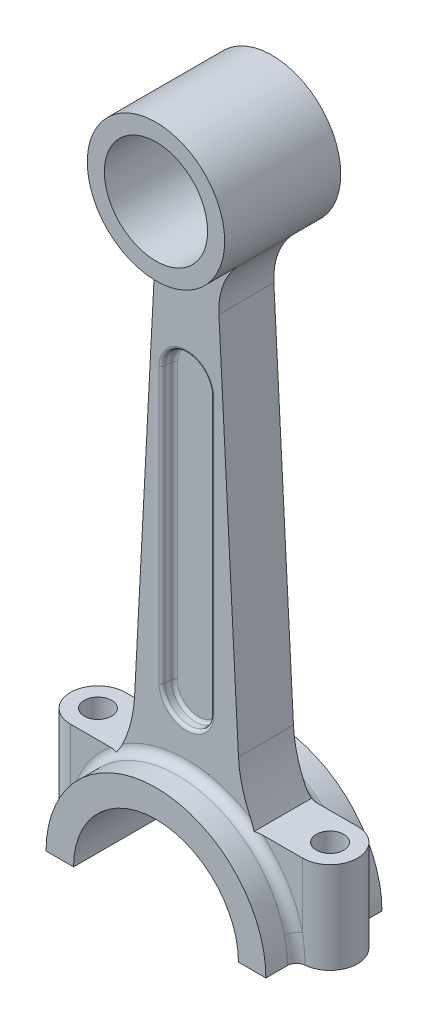
SolidWorks part; units mm, degrees
ref_plane "Front Plane" through (0, 0, 0) normal (0, 0, 1) x (1, 0, 0)
ref_plane "Top Plane" through (0, 0, 0) normal (0, 1, 0) x (1, 0, 0)
ref_plane "Right Plane" through (0, 0, 0) normal (1, 0, 0) x (0, 0, -1)
sketch "Sketch1" plane through (0, 0, 0) normal (0, 0, 1) x (1, 0, 0)
  line L0 (0, 0) -> (0, -202.2) construction
  line L1 (-10, -20.1556) -> (-17.9037, -170.9677)
  line L2 (10, -20.1556) -> (17.9037, -170.9677)
  line L3 (-36, -202.2) -> (-27, -202.2)
  line L4 (27, -202.2) -> (36, -202.2)
  circle A0 centre (0, 0) radius 22.5
  circle A1 centre (0, 0) radius 16.9
  arc A2 (27, -202.2) -> (-27, -202.2) centre (0, -202.2) ccw
  arc A3 (36, -202.2) -> (-36, -202.2) centre (0, -202.2) ccw
  dimension "D1" = 33.8
  dimension "D2" = 45
  dimension "D3" = 54
  dimension "D4" = 72
  dimension "D5" = 202.2
  dimension "D6" = 20
  dimension "D7" = 6
extrude "Boss-Extrude1" add sketch "Sketch1" along normal mid plane 38 contours A3 A2 | A0 | A1 | L3 A2 L4 A3 region at (0, -167.005, 0)
extrude "Boss-Extrude2" add sketch "Sketch1<3>" along normal mid plane 18 contours A0 L0 A3 L2 | L0 A0 L1 A3 region at (7.1998, -101.43, 0) region at (-7.1998, -101.43, 0)
sketch "Sketch1<3>" plane through (0, 0, 0) normal (0, 0, 1) x (1, 0, 0) same geometry as "Sketch1"
sketch "Sketch2" plane through (0, 0, 9) normal (0, 0, 1) x (1, 0, 0)
  line L0 (0, 0) -> (0, -202.2) construction
  line L1 (0, -56.1) -> (0, -146.1) construction
  line L2 (8, -56.1) -> (8, -146.1)
  line L3 (-8, -56.1) -> (-8, -146.1)
  arc A0 (8, -56.1) -> (-8, -56.1) centre (0, -56.1) ccw
  arc A1 (-8, -146.1) -> (8, -146.1) centre (0, -146.1) ccw
  point P6 (0, -101.1)
  dimension "D2" = 8
  dimension "D1" = 90
extrude "Cut-Extrude1" cut sketch "Sketch2" against normal blind 4
mirror "Mirror1" about plane through (0, 0, 0) normal (0, 0, 1) of "Cut-Extrude1"
fillet "Fillet1" radius 1 16 edges at (0, -48.1, -9) (8, -101.1, -9) (0, -154.1, -9) (0, -48.1, -5) (8, -101.1, -5) (0, -154.1, -5) (0, -48.1, 9) (8, -101.1, 9) (0, -154.1, 9) (0, -48.1, 5) (8, -101.1, 5) (0, -154.1, 5) (-8, -101.1, -9) (-8, -101.1, -5) (-8, -101.1, 9) (-8, -101.1, 5)
fillet "Fillet3" radius 40 2 edges at (-17.9037, -170.9677, 0) (17.9037, -170.9677, 0)
ref_plane "Plane1" through (0, -172.2, 0) normal (0, -1, 0) x (-1, 0, 0)
sketch "Sketch3" plane through (0, -172.2, 0) normal (0, -1, 0) x (-1, 0, 0)
  line L0 (-38, 0) -> (38, 0) construction
  line L1 (-38, 9) -> (38, 9)
  line L2 (-38, -9) -> (38, -9)
  arc A0 (-38, 9) -> (-38, -9) centre (-38, 0) ccw
  arc A1 (38, -9) -> (38, 9) centre (38, 0) ccw
  point P2 (0, 0)
  dimension "D2" = 9
  dimension "D1" = 76
extrude "Boss-Extrude3" add sketch "Sketch3" along normal up to surface (30 mm away) up to face at (31.5, -202.2, 0)
sketch "Sketch5" plane through (0, 0, -9) normal (0, 0, -1) x (-1, 0, 0)
  line L1 (-27, -202.2) -> (27, -202.2)
  line L2 (-27, -202.2) -> (27, -202.2)
  arc A1 (27, -202.2) -> (-27, -202.2) centre (0, -202.2) ccw
  arc A2 (27, -202.2) -> (-27, -202.2) centre (0, -202.2) ccw
  dimension "D1" = 0
extrude "Cut-Extrude2" cut sketch "Sketch5" against normal through all
sketch "Sketch6" plane through (0, -172.2, 0) normal (0, 1, 0) x (1, 0, 0)
  circle A0 centre (-38, 0) radius 4.5
  dimension "D1" = 9
extrude "Cut-Extrude3" cut sketch "Sketch6" against normal through all
mirror "Mirror2" about plane through (0, 0, 0) normal (1, 0, 0) of "Cut-Extrude3"
fillet "Fillet2" radius 22.5 2 edges at (10, -20.1556, 0) (-10, -20.1556, 0)
fillet "Fillet4" radius 3 2 edges at (0, -166.2, 9) (0, -166.2, -9)
